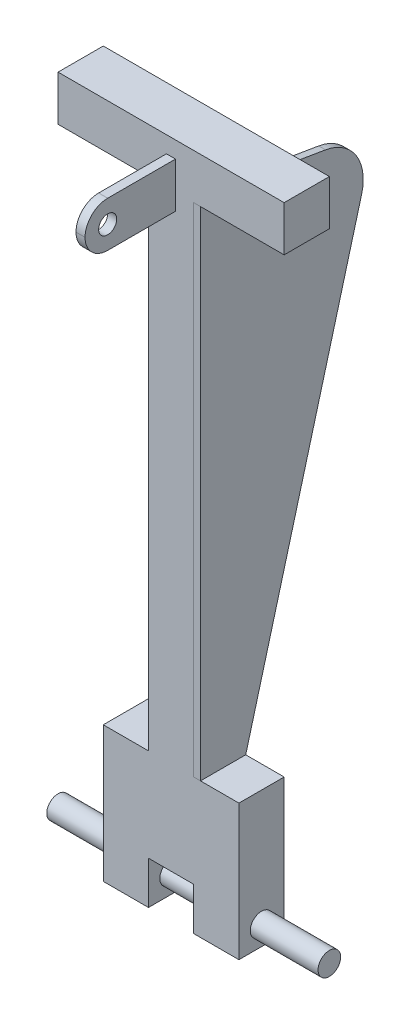
SolidWorks part; units mm, degrees
ref_plane "Front Plane" through (0, 0, 0) normal (0, 0, 1) x (1, 0, 0)
ref_plane "Top Plane" through (0, 0, 0) normal (0, 1, 0) x (1, 0, 0)
ref_plane "Right Plane" through (0, 0, 0) normal (1, 0, 0) x (0, 0, -1)
sketch "Sketch1" plane through (0, 0, 0) normal (0, 0, 1) x (1, 0, 0)
  line L0 (0, 82.1837) -> (0, -54.4245) construction
  line L1 (15, -70) -> (15, -40)
  line L3 (5, -70) -> (5, 70)
  line L4 (5, 70) -> (-5, 70)
  line L5 (-5, -70) -> (-5, 70)
  line L6 (5, -70) -> (-5, 70) construction
  line L7 (5, 70) -> (-5, -70) construction
  line L8 (-25, 80) -> (25, 80)
  line L9 (-25, 80) -> (-25, 70)
  line L10 (-25, 70) -> (25, 70)
  line L11 (25, 80) -> (25, 70)
  line L12 (-25, 80) -> (25, 70) construction
  line L13 (-25, 70) -> (25, 80) construction
  line L14 (-5, -70) -> (-15, -70)
  line L15 (-5, -70) -> (-5, -40)
  line L16 (-5, -40) -> (-15, -40)
  line L17 (-15, -70) -> (-15, -40)
  line L18 (5, -40) -> (15, -40)
  line L19 (5, -70) -> (15, -70)
  line L20 (-5, -60.5553) -> (5, -60.5553)
  point P3 (0, 0)
  point P8 (0, 75)
  dimension "D1" = 10
  dimension "D2" = 140
  dimension "D3" = 10
  dimension "D4" = 5
  dimension "D5" = 50
  dimension "D6" = 10
  dimension "D7" = 30
extrude "Boss-Extrude1" add sketch "Sketch1" along normal blind 10 contours L11 L8 L9 L10 L4 | L5 L3 L4 | L17 L14 L5 L16 | L3 L19 L1 L18 region at (10, -55, 0) region at (0, 4.7224, 0) region at (0, 75, 0) region at (-10, -55, 0)
sketch "Sketch2" plane through (15, 0, 0) normal (1, 0, 0) x (0, 0, -1)
  circle A0 centre (-5, -65.7096) radius 2.5
sketch "Sketch5" plane through (0, 0, 10) normal (0, 0, 1) x (1, 0, 0)
  line L1 (-1.0254, 66.3382) -> (0.9746, 66.3382)
  line L2 (-1.0254, 66.3382) -> (-1.0254, 76.3382)
  line L3 (-1.0254, 76.3382) -> (0.9746, 76.3382)
  line L4 (0.9746, 66.3382) -> (0.9746, 76.3382)
  line L5 (-1.0254, 66.3382) -> (0.9746, 76.3382) construction
  line L6 (-1.0254, 76.3382) -> (0.9746, 66.3382) construction
  point P0 (-0.0254, 71.3382)
  dimension "D1" = 10
  dimension "D2" = 2
extrude "Boss-Extrude2" add sketch "Sketch5" along normal blind 20
fillet "Fillet1" radius 5 2 edges at (-0.0254, 66.3382, 30) (-0.0254, 76.3382, 30)
sketch "Sketch6" plane through (0.9746, 0, 0) normal (1, 0, 0) x (0, 0, -1)
  circle A0 centre (-25, 71.3382) radius 2
extrude "Cut-Extrude2" cut sketch "Sketch6" against normal blind 20
sketch "Sketch7" plane through (5, 0, 0) normal (1, 0, 0) x (0, 0, -1)
  line L0 (0, 70) -> (17.646, 67.0404)
  line L1 (25.6433, 54.5609) -> (0, -40)
  line L3 (0, 70) -> (-10, 70)
  line L4 (-10, 70) -> (-10, -40)
  line L5 (-10, -40) -> (0, -40)
  arc A0 (17.646, 67.0404) -> (25.6433, 54.5609) centre (15.9919, 57.1782) cw
  dimension "D1" = 10
extrude "Boss-Extrude3" add sketch "Sketch7" along normal blind 1.5 separate body
extrude "Boss-Extrude4" add sketch "Sketch2" along normal blind 15 and the other way blind 45 contours A0
